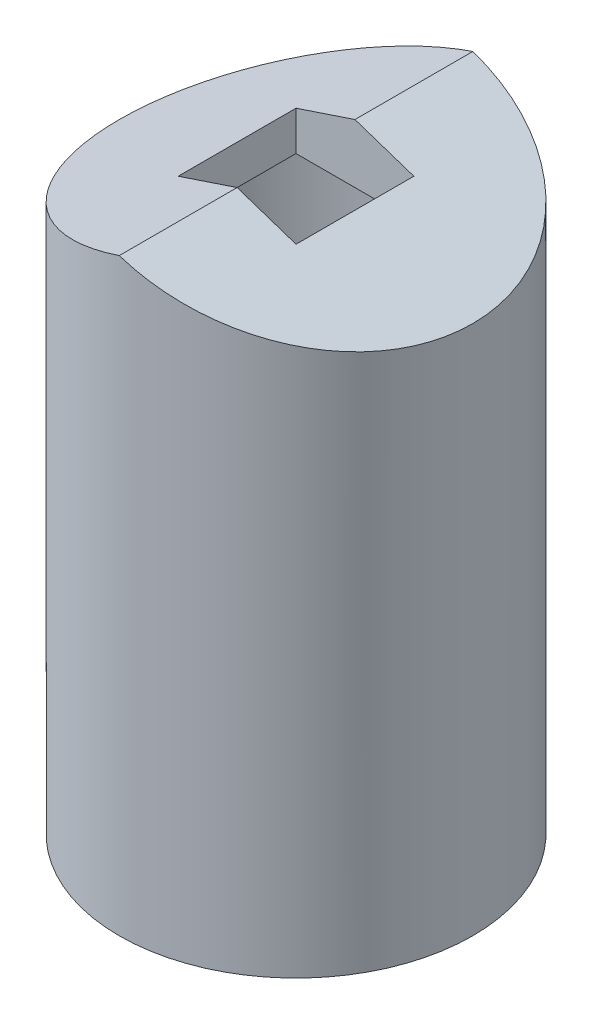
SolidWorks part; units mm, degrees
ref_plane "Front Plane" through (0, 0, 0) normal (0, 0, 1) x (1, 0, 0)
ref_plane "Top Plane" through (0, 0, 0) normal (0, 1, 0) x (1, 0, 0)
ref_plane "Right Plane" through (0, 0, 0) normal (1, 0, 0) x (0, 0, -1)
sketch "Sketch1" plane through (0, 0, 0) normal (0, 0, 1) x (1, 0, 0)
  line L0 (0, 0) -> (0, 27) construction
  line L1 (0, 27) -> (9, 27)
  line L2 (9, 24.5885) -> (9, 0)
  line L3 (9, 0) -> (0, 0)
  line L4 (0, 0) -> (0, 27)
  line L5 (9, 27) -> (9, 24.5885)
  dimension "D1" = 27
  dimension "D2" = 9
revolve "Revolve4" add sketch "Sketch1" angle 360 about L4
sketch "Sketch6" plane through (0, 0, 0) normal (0, 0, 1) x (1, 0, 0)
  line L0 (0, 27) -> (0, 30)
  line L1 (9, 27) -> (-9, 27) construction
  line L2 (0, 30) -> (9, 27)
  line L4 (0, 30) -> (-9, 27)
  line L5 (-9, 27) -> (0, 27)
  line L6 (0, 27) -> (9, 27)
  dimension "D1" = 3
extrude "Boss-Extrude3" add sketch "Sketch6" against normal through all and the other way blind 9 contours L0 L6 L2 | L4 L5 L0 region at (-3, 28, 0) region at (3, 28, 0)
sketch "Sketch7" plane through (0, 0, 0) normal (0, -1, 0) x (1, 0, 0)
  circle A0 centre (0, 0) radius 9
  circle A1 centre (0, 0) radius 14.6423
extrude "Cut-Extrude3" cut sketch "Sketch7" against normal blind 32
sketch "Sketch8" plane through (0, 0, 0) normal (0, -1, 0) x (-1, 0, 0)
  line L1 (3, -3) -> (-3, -3)
  line L2 (3, -3) -> (3, 3)
  line L3 (3, 3) -> (-3, 3)
  line L4 (-3, -3) -> (-3, 3)
  line L5 (3, -3) -> (-3, 3) construction
  line L6 (3, 3) -> (-3, -3) construction
  point P0 (0, 0)
  dimension "D1" = 6
  dimension "D2" = 6
extrude "Cut-Extrude4" cut sketch "Sketch8" against normal blind 32
sketch "Sketch9" plane through (0, 0, 0) normal (0, -1, 0) x (1, 0, 0)
  circle A0 centre (0, 0) radius 8
  dimension "D1" = 16
extrude "Cut-Extrude5" cut sketch "Sketch9" against normal blind 27
